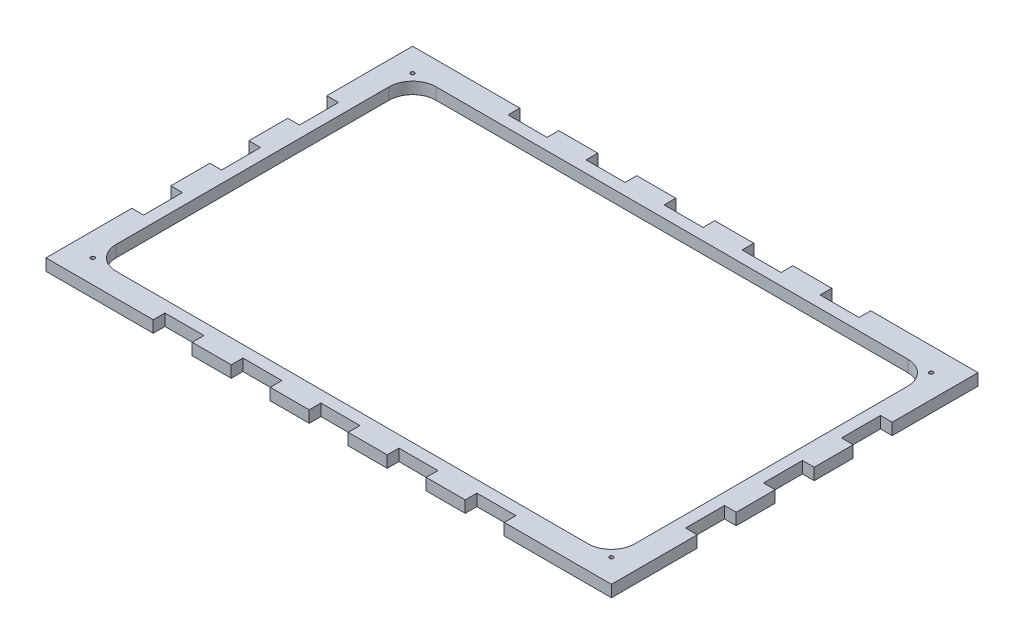
SolidWorks part; units mm, degrees
material "Maple"
ref_plane "Front Plane" through (0, 0, 0) normal (0, 0, 1) x (1, 0, 0)
ref_plane "Top Plane" through (0, 0, 0) normal (0, 1, 0) x (1, 0, 0)
ref_plane "Right Plane" through (0, 0, 0) normal (1, 0, 0) x (0, 0, -1)
sketch "Sketch1" plane through (0, 0, 0) normal (0, 1, 0) x (1, 0, 0)
  line L1 (0, 0) -> (145, 0)
  line L2 (0, 0) -> (0, -94)
  line L3 (0, -94) -> (145, -94)
  line L4 (145, 0) -> (145, -94)
  dimension "D1" = 145
  dimension "D2" = 94
extrude "Boss-Extrude1" add sketch "Sketch1" along normal blind 3
sketch "Sketch2" plane through (0, 3, 0) normal (0, 1, 0) x (1, 0, 0)
  line L0 (145, 0) -> (0, 0) construction
  line L1 (6, -6) -> (139, -6)
  line L2 (6, -6) -> (6, -88)
  line L3 (6, -88) -> (139, -88)
  line L4 (139, -6) -> (139, -88)
  line L5 (0, -94) -> (145, -94) construction
  line L6 (0, 0) -> (0, -94) construction
  line L7 (145, -94) -> (145, 0) construction
  dimension "D1" = 6
  dimension "D2" = 6
  dimension "D3" = 6
  dimension "D4" = 6
extrude "Cut-Extrude1" cut sketch "Sketch2" against normal through all
fillet "Fillet1" radius 6 4 edges at (139, 1.5, 88) (139, 1.5, 6) (6, 1.5, 6) (6, 1.5, 88)
sketch "Sketch3" plane through (0, 0, 0) normal (0, -1, 0) x (1, 0, 0)
  line L0 (145, 0) -> (0, 0) construction
  line L1 (0, 0) -> (0, 94) construction
  line L2 (0, 94) -> (145, 94) construction
  line L3 (145, 94) -> (145, 0) construction
  circle A0 centre (6, 88) radius 0.5
  circle A1 centre (139, 88) radius 0.5
  circle A2 centre (139, 6) radius 0.5
  circle A3 centre (6, 6) radius 0.5
  dimension "D1" = 1
  dimension "D2" = 1
  dimension "D3" = 1
  dimension "D4" = 1
  dimension "D5" = 6
  dimension "D6" = 6
  dimension "D7" = 6
  dimension "D8" = 6
  dimension "D9" = 6
  dimension "D10" = 6
  dimension "D11" = 6
  dimension "D12" = 6
extrude "Cut-Extrude2" cut sketch "Sketch3" against normal through all
sketch "Sketch8" plane through (0, 0, 0) normal (0, -1, 0) x (-1, 0, 0)
  line L0 (-72.5, -94) -> (-72.5, 0) construction
  line L1 (0, -94) -> (-145, -94) construction
  line L2 (-145, 0) -> (0, 0) construction
  line L4 (-67.5, -94) -> (-77.5, -94)
  line L5 (-67.5, -94) -> (-67.5, -91)
  line L6 (-67.5, -91) -> (-77.5, -91)
  line L7 (-77.5, -94) -> (-77.5, -91)
  line L8 (-67.5, -94) -> (-77.5, -91) construction
  line L9 (-67.5, -91) -> (-77.5, -94) construction
  line L10 (-67.5, -3) -> (-77.5, -3)
  line L11 (-67.5, -3) -> (-67.5, 0)
  line L12 (-67.5, 0) -> (-77.5, 0)
  line L13 (-77.5, -3) -> (-77.5, 0)
  line L14 (-67.5, -3) -> (-77.5, 0) construction
  line L15 (-67.5, 0) -> (-77.5, -3) construction
  point P6 (-72.5, -92.5)
  point P11 (-72.5, -1.5)
  dimension "D1" = 3
  dimension "D2" = 10
extrude "Cut-Extrude5" cut sketch "Sketch8" against normal through all
pattern_linear "LPattern3" count 4 spacing 20 along (1, 0, 0) count 4 spacing 20 along (-1, 0, 0) of "Cut-Extrude5" pattern seed only yes
sketch "Sketch9" plane through (0, 0, 0) normal (0, -1, 0) x (-1, 0, 0)
  line L0 (0, -47) -> (-145, -47) construction
  line L1 (0, 0) -> (0, -94) construction
  line L2 (-145, -94) -> (-145, 0) construction
  line L4 (0, -52) -> (-3, -52)
  line L5 (0, -52) -> (0, -42)
  line L6 (0, -42) -> (-3, -42)
  line L7 (-3, -52) -> (-3, -42)
  line L8 (0, -52) -> (-3, -42) construction
  line L9 (0, -42) -> (-3, -52) construction
  line L10 (-142, -52) -> (-145, -52)
  line L11 (-142, -52) -> (-142, -42)
  line L12 (-142, -42) -> (-145, -42)
  line L13 (-145, -52) -> (-145, -42)
  line L14 (-142, -52) -> (-145, -42) construction
  line L15 (-142, -42) -> (-145, -52) construction
  point P6 (-1.5, -47)
  point P11 (-143.5, -47)
  dimension "D1" = 3
  dimension "D2" = 10
extrude "Cut-Extrude6" cut sketch "Sketch9" against normal through all
pattern_linear "LPattern4" count 3 spacing 20 along (0, 0, 1) count 3 spacing 20 along (0, 0, -1) of "Cut-Extrude6" pattern seed only yes
sketch "Sketch11" plane through (0, 0, 0) normal (0, -1, 0) x (-1, 0, 0)
  line L1 (-145, -82) -> (-142, -82)
  line L2 (-145, -82) -> (-145, -92)
  line L3 (-145, -92) -> (-142, -92)
  line L4 (-142, -82) -> (-142, -92)
  line L5 (-127.5, -94) -> (-137.5, -94)
  line L6 (-127.5, -94) -> (-127.5, -91)
  line L7 (-127.5, -91) -> (-137.5, -91)
  line L8 (-137.5, -94) -> (-137.5, -91)
  line L9 (-127.5, 0) -> (-137.5, 0)
  line L10 (-127.5, 0) -> (-127.5, -3)
  line L11 (-127.5, -3) -> (-137.5, -3)
  line L12 (-137.5, 0) -> (-137.5, -3)
  line L13 (-145, -12) -> (-142, -12)
  line L14 (-145, -12) -> (-145, -2)
  line L15 (-145, -2) -> (-142, -2)
  line L16 (-142, -12) -> (-142, -2)
  line L17 (0, -12) -> (-3, -12)
  line L18 (0, -12) -> (0, -2)
  line L19 (0, -2) -> (-3, -2)
  line L20 (-3, -12) -> (-3, -2)
  line L21 (-17.5, -3) -> (-7.5, -3)
  line L22 (-17.5, -3) -> (-17.5, 0)
  line L23 (-17.5, 0) -> (-7.5, 0)
  line L24 (-7.5, -3) -> (-7.5, 0)
  line L25 (0, -92) -> (-3, -92)
  line L26 (0, -92) -> (0, -82)
  line L27 (0, -82) -> (-3, -82)
  line L28 (-3, -92) -> (-3, -82)
  line L29 (-17.5, -94) -> (-7.5, -94)
  line L30 (-17.5, -94) -> (-17.5, -91)
  line L31 (-17.5, -91) -> (-7.5, -91)
  line L32 (-7.5, -94) -> (-7.5, -91)
extrude "Boss-Extrude4" add sketch "Sketch11" against normal through all
equation "\"D2@Sketch2\"=\"D1@Sketch2\""
equation "\"D3@Sketch2\"=\"D1@Sketch2\""
equation "\"D4@Sketch2\"=\"D1@Sketch2\""
equation "\"D2@Sketch3\"=\"D1@Sketch3\""
equation "\"D3@Sketch3\"=\"D1@Sketch3\""
equation "\"D4@Sketch3\"=\"D1@Sketch3\""
equation "\"D7@Sketch3\"=\"D6@Sketch3\""
equation "\"D8@Sketch3\"=\"D7@Sketch3\""
equation "\"D9@Sketch3\"=\"D5@Sketch3\""
equation "\"D10@Sketch3\"=\"D6@Sketch3\""
equation "\"D11@Sketch3\"=\"D7@Sketch3\""
equation "\"D12@Sketch3\"=\"D8@Sketch3\""
